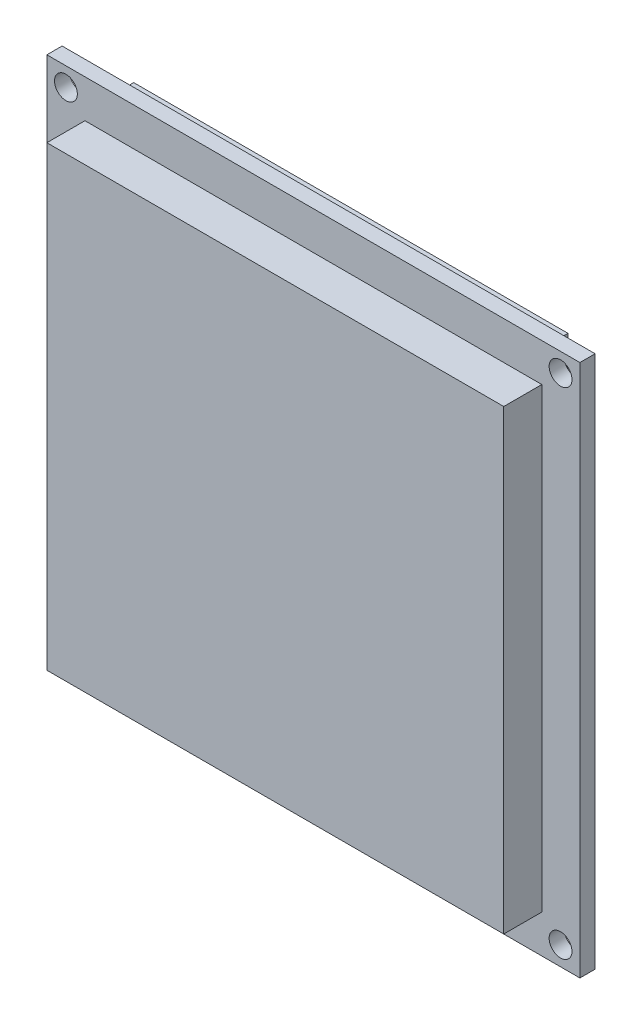
SolidWorks part; units mm, degrees
other "PCB components"
other "connector"
other "Antenna"
other "PCB"
ref_plane "Ebene vorne" through (0, 0, 0) normal (0, 0, 1) x (1, 0, 0)
ref_plane "Ebene oben" through (0, 0, 0) normal (0, 1, 0) x (1, 0, 0)
ref_plane "Ebene rechts" through (0, 0, 0) normal (1, 0, 0) x (0, 0, -1)
sketch "Sketch1" plane through (0, 0, 0) normal (0, 0, 1) x (1, 0, 0)
  line L0 (-29.98, -30.02) -> (-29.98, 29.98)
  line L1 (35.02, -35.02) -> (-34.98, -35.02)
  line L2 (35.02, -35.02) -> (35.02, 34.98)
  line L3 (35.02, 34.98) -> (-34.98, 34.98)
  line L4 (-34.98, -35.02) -> (-34.98, 34.98)
  line L5 (35.02, -35.02) -> (-34.98, 34.98) construction
  line L6 (-34.98, -31.02) -> (-30.98, -31.02) construction
  line L7 (30.02, 29.98) -> (-29.98, 29.98)
  line L8 (30.02, -30.02) -> (30.02, 29.98)
  line L9 (30.02, -30.02) -> (-29.98, -30.02)
  line L10 (-30.98, -31.02) -> (-30.98, -35.02) construction
  line L11 (0, -38.5) -> (0, 38.5) construction
  line L13 (38.5, 0) -> (-38.5, 0) construction
  line L14 (-28.5745, 32.52) -> (28.4514, 32.52)
  line L15 (-28.5745, 32.52) -> (-28.5745, 11.4524)
  line L16 (-28.5745, 11.4524) -> (28.4514, 11.4524)
  line L17 (28.4514, 32.52) -> (28.4514, 11.4524)
  line L19 (11.0829, -35.02) -> (11.0829, -28.4263)
  line L20 (11.0829, -28.4263) -> (-11.0428, -28.4263)
  line L21 (-11.0428, -35.02) -> (-11.0428, -28.4263)
  line L22 (-11.0428, -35.02) -> (11.0829, -35.02)
  line L23 (-11.0428, -35.02) -> (-11.0428, -30.02)
  line L24 (-11.0428, -30.02) -> (11.0829, -30.02)
  line L25 (11.0829, -35.02) -> (11.0829, -30.02)
  circle A0 centre (-32.48, -32.52) radius 1.5
  circle A1 centre (32.48, -32.52) radius 1.5
  circle A2 centre (32.48, 32.52) radius 1.5
  circle A3 centre (-32.48, 32.52) radius 1.5
  point P0 (0, 0)
  point P29 (0.02, -35.02)
  dimension "D4" = 3
  dimension "D1" = 70
  dimension "D2" = 70
  dimension "D5" = 4
  dimension "D3" = 5
extrude "Boss-Extrude1" add sketch "Sketch1" along normal blind 2 contours L4 L1 L2 L3 A1 A0 L8 L9 L0 L7 A2 A3 | L23 L22 L25 L24 | L15 L14 L17 L16 | L0 L7 L8 L9 region at (-20.5114, -31.01, 0)
extrude "Boss-Extrude4" add sketch "Sketch1<4>" along normal offset from surface (7 mm away) 5 separate body contours L9 L0 L7 L8 up to face at (0.02, -0.02, 2) offset beyond the face yes
sketch "Sketch1<4>" plane through (0, 0, 0) normal (0, 0, 1) x (1, 0, 0) same geometry as "Sketch1"
extrude "Boss-Extrude5" add sketch "Sketch1<5>" against normal blind 3 separate body contours L21 L9 L19 L20 | L21 L1 L19 L9 | L17 L14 L15 L7 | L17 L7 L15 L16 region at (0.02, -29.2232, 0) region at (0.02, -32.52, 0) region at (-0.0615, 31.25, 0) region at (-0.0615, 20.7162, 0)
sketch "Sketch1<5>" plane through (0, 0, 0) normal (0, 0, 1) x (1, 0, 0) same geometry as "Sketch1"
extrude "Cut-Extrude1" cut sketch "Sketch1<6>" along normal up to surface (2 mm away) contours L0 L7 L8 L9 up to face at (0.02, -0.02, 2)
sketch "Sketch1<6>" plane through (0, 0, 0) normal (0, 0, 1) x (1, 0, 0) same geometry as "Sketch1"
sketch "Sketch4" plane through (0, -35.02, 0) normal (0, -1, 0) x (1, 0, 0)
  line L8 (10.5829, -0.5) -> (-10.5428, -0.5)
  line L9 (-10.5428, -0.5) -> (-10.5428, -2.5)
  line L10 (-10.5428, -2.5) -> (10.5829, -2.5)
  line L11 (10.5829, -2.5) -> (10.5829, -0.5)
  line L12 (10.5829, -0.5) -> (-10.5428, -0.5)
  line L13 (-10.5428, -0.5) -> (-10.5428, -2.5)
  line L14 (-10.5428, -2.5) -> (10.5829, -2.5)
  line L15 (10.5829, -2.5) -> (10.5829, -0.5)
  dimension "D1" = 0.5
extrude "Cut-Extrude2" cut sketch "Sketch4" against normal offset from surface (5.5937 mm away) 1 up to face at (0.02, -28.4263, -1.5)
